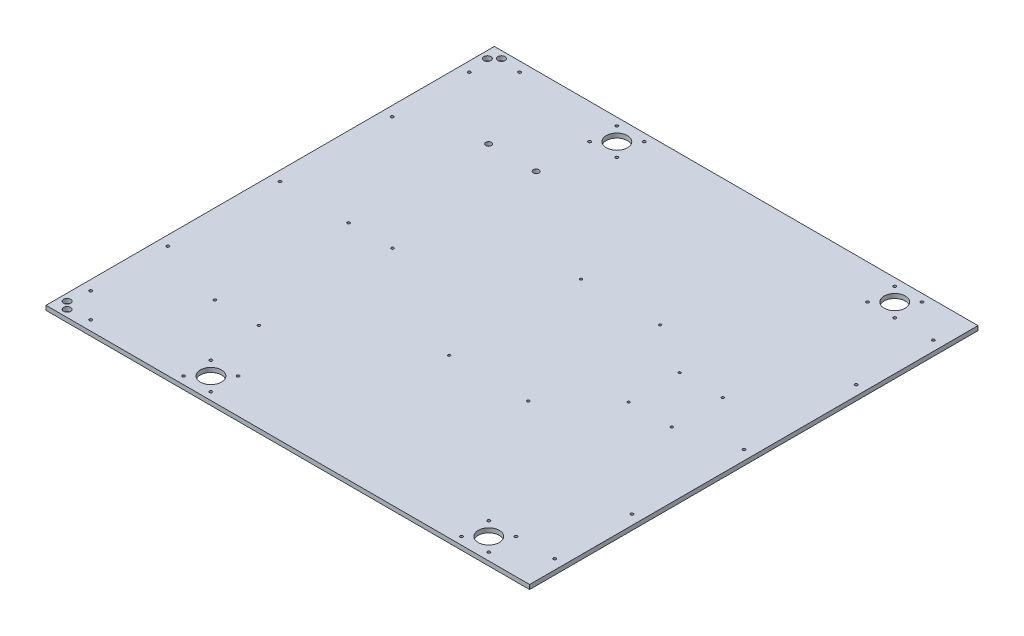
SolidWorks part; units mm, degrees
ref_plane "Front Plane" through (0, 0, 0) normal (0, 0, 1) x (1, 0, 0)
ref_plane "Top Plane" through (0, 0, 0) normal (0, 1, 0) x (1, 0, 0)
ref_plane "Right Plane" through (0, 0, 0) normal (1, 0, 0) x (0, 0, -1)
sketch "Sketch1" plane through (0, 0, 0) normal (1, 0, 0) x (0, 0, -1)
  line L0 (0, 0) -> (-510, 0)
  line L1 (-510, 0) -> (-510, 5)
  line L2 (-510, 5) -> (0, 5)
  line L6 (0, 5) -> (0, 0)
  dimension "D1" = 510
  dimension "D2" = 5
extrude "Boss-Extrude1" add sketch "Sketch1" along normal blind 550
sketch "BotthomHoles-Sketch2" plane through (0, 5, 0) normal (0, 1, 0) x (1, 0, 0)
  line L0 (550, -3.175) -> (0, -3.175) construction
  line L2 (550, 0) -> (550, -510) construction
  line L3 (550, 0) -> (0, 0) construction
  line L4 (550, -510) -> (0, -510) construction
  line L7 (0, 0) -> (0, -510) construction
  line L8 (550, 0) -> (550, -510) construction
  circle A0 centre (479.425, -24.175) radius 12
  circle A2 centre (463.925, -8.675) radius 1.5875
  circle A3 centre (494.925, -8.675) radius 1.5875
  circle A6 centre (463.925, -39.675) radius 1.5875
  circle A7 centre (494.925, -39.675) radius 1.5875
  circle A8 centre (39.6875, -11.1125) radius 1.5875
  circle A10 centre (178.925, -39.675) radius 1.5875
  circle A11 centre (147.925, -39.675) radius 1.5875
  circle A12 centre (178.925, -8.675) radius 1.5875
  circle A13 centre (147.925, -8.675) radius 1.5875
  circle A14 centre (163.425, -24.175) radius 12
  circle A15 centre (39.6875, -498.8875) radius 1.5875
  circle A16 centre (147.925, -501.325) radius 1.5875
  circle A17 centre (178.925, -501.325) radius 1.5875
  circle A18 centre (147.925, -470.325) radius 1.5875
  circle A19 centre (178.925, -470.325) radius 1.5875
  circle A20 centre (463.925, -470.325) radius 1.5875
  circle A21 centre (463.925, -501.325) radius 1.5875
  circle A22 centre (494.925, -470.325) radius 1.5875
  circle A23 centre (494.925, -501.325) radius 1.5875
  circle A25 centre (163.425, -485.825) radius 12
  circle A26 centre (479.425, -485.825) radius 12
  circle A27 centre (11.1125, -39.6875) radius 1.5875
  circle A28 centre (11.1125, -127.5) radius 1.5875
  circle A29 centre (11.1125, -255) radius 1.5875
  circle A30 centre (11.1125, -382.5) radius 1.5875
  circle A31 centre (11.1125, -470.3125) radius 1.5875
  circle A32 centre (538.8875, -470.3125) radius 1.5875
  circle A33 centre (538.8875, -382.5) radius 1.5875
  circle A34 centre (538.8875, -255) radius 1.5875
  circle A35 centre (538.8875, -127.5) radius 1.5875
  circle A36 centre (538.8875, -39.6875) radius 1.5875
  dimension "D9" = 3.175
  dimension "D10" = 24
  dimension "D13" = 3.175
  dimension "D29" = 3.175
  dimension "D2" = 8.675
  dimension "D5" = 15.5
  dimension "D6" = 31
  dimension "D7" = 15.5
  dimension "D8" = 31
  dimension "D11" = 21
  dimension "D12" = 39.6875
  dimension "D15" = 31
  dimension "D16" = 15.5
  dimension "D17" = 316
  dimension "D3" = 70.575
  dimension "D4" = 11.1125
  dimension "D18" = 8.675
  dimension "D19" = 15.5
  dimension "D20" = 31
  dimension "D21" = 11.1125
  dimension "D22" = 39.6875
  dimension "D23" = 39.6875
  dimension "D24" = 127.5
  dimension "D25" = 127.5
  dimension "D26" = 127.5
  dimension "D27" = 11.1125
  dimension "D28" = 11.1125
  dimension "D14" = 163.425
extrude "BottomHoles-Cut-Extrude1" cut sketch "BotthomHoles-Sketch2" against normal through all
sketch "BottomPSUHolesSketch2" plane through (0, 5, 0) normal (0, 1, 0) x (1, 0, 0)
  line L0 (0, 0) -> (0, -510) construction
  line L3 (550, 0) -> (0, 0) construction
  line L4 (550, -510) -> (0, -510) construction
  circle A0 centre (90.8, -256.7) radius 1.5
  circle A1 centre (140.8, -256.7) radius 1.5
  circle A2 centre (90.8, -408.7) radius 1.5
  circle A3 centre (140.8, -408.7) radius 1.5
  circle A6 centre (92.8, -99.3) radius 3.25
  circle A7 centre (146.8, -99.3) radius 3.25
  dimension "D6" = 3
  dimension "D4" = 6.5
  dimension "D1" = 152
  dimension "D2" = 50
  dimension "D3" = 90.8
  dimension "D7" = 54
  dimension "D8" = 2
  dimension "D9" = 99.3
  dimension "D5" = 101.3
extrude "BottomPSUHolesCut-Extrude1" cut sketch "BottomPSUHolesSketch2" against normal through all
sketch "BottomMainboardHolesSketch2" plane through (0, 5, 0) normal (0, 1, 0) x (1, 0, 0)
  line L0 (550, 0) -> (0, 0) construction
  line L1 (0, 0) -> (0, -510) construction
  line L2 (550, 0) -> (550, -510) construction
  line L3 (550, -510) -> (0, -510) construction
  circle A0 centre (278.5, -180) radius 1.35
  circle A1 centre (368.5, -180) radius 1.35
  circle A2 centre (278.5, -330) radius 1.35
  circle A3 centre (368.5, -330) radius 1.35
  circle A4 centre (426.7, -216) radius 1.35
  circle A5 centre (475.7, -216) radius 1.35
  circle A6 centre (426.7, -274) radius 1.35
  circle A7 centre (475.7, -274) radius 1.35
  dimension "D6" = 2.7
  dimension "D7" = 2.7
  dimension "D1" = 90
  dimension "D2" = 150
  dimension "D3" = 180
  dimension "D4" = 58
  dimension "D5" = 49
  dimension "D8" = 216
  dimension "D9" = 278.5
  dimension "D10" = 74.3
  dimension "D11" = 236
extrude "BottomMainboardHolesCut-Extrude1" cut sketch "BottomMainboardHolesSketch2" against normal through all
sketch "CableHolesSketch2" plane through (0, 5, 0) normal (0, 1, 0) x (1, 0, 0)
  line L0 (550, 0) -> (0, 0) construction
  line L1 (550, -510) -> (0, -510) construction
  line L2 (0, 0) -> (0, -510) construction
  circle A0 centre (8, -494) radius 4
  circle A1 centre (16, -502) radius 4
  circle A2 centre (8, -16) radius 4
  circle A3 centre (16, -8) radius 4
  dimension "D6" = 8
  dimension "D1" = 16
  dimension "D2" = 16
  dimension "D3" = 16
  dimension "D4" = 8
  dimension "D5" = 8
  dimension "D7" = 8
extrude "CableHolesCut-Extrude1" cut sketch "CableHolesSketch2" against normal through all
equation "\"LowerRailWidth\"= 2.00in"
equation "\"RailThickness\"= .125in'Spec"
equation "\"StepperHoleDiameter\"= 24mm"
equation "\"StepperMountingHoleDiameter\"= 3.175mm"
equation "\"SideRailLength\"= 550mm"
equation "\"StepperMountingHoleDistance\"= 31mm'Spec"
equation "\"StepperMountingHoleOffsetFromLeftOrRightSide\"= \"StepperMountingHoleOffsetFromItsSide\" + \"RailThickness\""
equation "\"HoleOffsetFromEdge\"= \"RailThickness\" * 2.5"
equation "\"HoleOffsetFromSide\"= \"RailThickness\" * 3.5"
equation "\"StepperMountingHoleOffsetFromItsSide\"= 5.5mm'Spec"
equation "\"FasteningHoleDiameter\"= .125in"
equation "\"D2@BotthomHoles-Sketch2\" = \"StepperMountingHoleOffsetFromLeftOrRightSide\""
equation "\"D5@BotthomHoles-Sketch2\" = \"StepperMountingHoleDistance\" / 2"
equation "\"D6@BotthomHoles-Sketch2\" = \"StepperMountingHoleDistance\""
equation "\"D7@BotthomHoles-Sketch2\" = \"StepperMountingHoleDistance\" / 2"
equation "\"D8@BotthomHoles-Sketch2\" = \"StepperMountingHoleDistance\""
equation "\"D9@BotthomHoles-Sketch2\" = \"StepperMountingHoleDiameter\""
equation "\"D10@BotthomHoles-Sketch2\" = \"StepperHoleDiameter\""
equation "\"D1@Boss-Extrude1\"=\"SideRailLength\""
equation "\"BedThirdSize\"= 70mm"
equation "\"BedInnerSquareWidth\"= \"BedThirdSize\" * 3'Equals 210"
equation "\"BedInnerSquareLength\"= \"BedInnerSquareWidth\""
equation "\"BedLWidth\"= \"BedThirdSize\"'Equals 70"
equation "\"BedLength\"= \"BedInnerSquareLength\" + \"BedLWidth\" * 2 + \"BedIncreasedByLength\"'Equals 350"
equation "\"DistanceBetweenFrontToBackStepperHoles\"= \"BedLength\" - \"DistanceFromBedFrontToFirstLeftStepperHole\"'Equals 316"
equation "\"DistanceFromBedFrontToFirstLeftStepperHole\"= \"LeadScrewNutPadSize\" + 10mm'Equals 34"
equation "\"DistanceFromFrontSideToBedFront\"= \"RailThickness\" + \"BeltTensionerDepth\" + 10mm'Equals 36.575"
equation "\"20TGT2PulleyDiameter\"= 17.9mm'Spec"
equation "\"BeltTensionerBackWallThickness\"= 4mm"
equation "\"BeltTensionerSpaceBetweenPulleyAndWall\"= 1.5mm"
equation "\"BeltTensionerInnerDepth\"= \"20TGT2PulleyDiameter\" + \"BeltTensionerSpaceBetweenPulleyAndWall\""
equation "\"BeltTensionerDepth\"= \"BeltTensionerBackWallThickness\" + \"BeltTensionerInnerDepth\"'Equals 23.4"
equation "\"BedIncreasedByLength\"= 0mm"
equation "\"LowerCornerBlockWidth\"= \"LowerRailWidth\" - \"RailThickness\" * 2'Room for left front stepper"
equation "\"D12@BotthomHoles-Sketch2\"=\"CornerEnclosureOffset\""
equation "\"D13@BotthomHoles-Sketch2\"=\"FasteningHoleDiameter\""
equation "\"CornerEnclosureOffset\"= \"LowerCornerBlockWidth\" - \"HoleOffsetFromEdge\" + \"RailThickness\""
equation "\"LowerCornerBlockY1FromSide\"= \"HoleOffsetFromSide\""
equation "\"D15@BotthomHoles-Sketch2\"=\"StepperMountingHoleDistance\""
equation "\"D16@BotthomHoles-Sketch2\"=\"StepperMountingHoleDistance\"/2"
equation "\"D17@BotthomHoles-Sketch2\"=\"DistanceBetweenFrontToBackStepperHoles\""
equation "\"DistanceFromFrontSideToFirstLeftStepperHole\"= \"DistanceFromFrontSideToBedFront\" + \"DistanceFromBedFrontToFirstLeftStepperHole\"'Equals 70.575"
equation "\"LeadScrewNutMountingHoleFlangeDiameter\"= 22mm'Spec"
equation "\"LeadScrewNutPadSize\"= \"LeadScrewNutMountingHoleFlangeDiameter\" + 2mm'Equals 24"
equation "\"D3@BotthomHoles-Sketch2\"=\"DistanceFromFrontSideToFirstLeftStepperHole\""
equation "\"LowerEnclosureThickness\"= 5mm"
equation "\"FrontBackRailLength\"= 510mm"
equation "\"D4@BotthomHoles-Sketch2\"=\"LowerCornerBlockY1FromSide\""
equation "\"D1@Sketch1\"=\"FrontBackRailLength\""
equation "\"D18@BotthomHoles-Sketch2\"=\"StepperMountingHoleOffsetFromLeftOrRightSide\""
equation "\"D19@BotthomHoles-Sketch2\"=\"StepperMountingHoleDistance\"/2"
equation "\"D20@BotthomHoles-Sketch2\"=\"StepperMountingHoleDistance\""
equation "\"D21@BotthomHoles-Sketch2\"=\"LowerCornerBlockY1FromSide\""
equation "\"D22@BotthomHoles-Sketch2\"=\"CornerEnclosureOffset\""
equation "\"D23@BotthomHoles-Sketch2\"=\"CornerEnclosureOffset\""
equation "\"FrontOrBackEnclosureOffsets\"= \"FrontBackRailLength\" / 4"
equation "\"D24@BotthomHoles-Sketch2\"=\"FrontOrBackEnclosureOffsets\""
equation "\"D25@BotthomHoles-Sketch2\"=\"FrontOrBackEnclosureOffsets\""
equation "\"D26@BotthomHoles-Sketch2\"=\"FrontOrBackEnclosureOffsets\""
equation "\"D27@BotthomHoles-Sketch2\"=\"LowerCornerBlockY1FromSide\""
equation "\"D28@BotthomHoles-Sketch2\"=\"LowerCornerBlockY1FromSide\""
equation "\"D29@BotthomHoles-Sketch2\"=\"FasteningHoleDiameter\""
equation "\"D2@Sketch1\"=\"LowerEnclosureThickness\""
equation "\"24VPSUMountingHolesShortDistanceBetween\"= 50mm'Yours may differ"
equation "\"24VPSUMountingHolesLongDistanceBetween\"= 152mm'Yours may differ"
equation "\"24VPSUMountingHoleOffsetFromEitherSide\"= 30mm'Yours may differ"
equation "\"24VPSUMountingHoleOffsetFromEdge\"= \"24VPSUMountingHoleOffsetFromEitherSide\" + \"LowerRailWidth\" + 10mm'Yours may differ"
equation "\"24VPSUMountingHoleDiameter\"= 3mm'Yours may differ"
equation "\"D2@BottomPSUHolesSketch2\" = \"24VPSUMountingHolesShortDistanceBetween\""
equation "\"D1@BottomPSUHolesSketch2\" = \"24VPSUMountingHolesLongDistanceBetween\""
equation "\"D3@BottomPSUHolesSketch2\" = \"24VPSUMountingHoleOffsetFromEdge\""
equation "\"D6@BottomPSUHolesSketch2\" = \"24VPSUMountingHoleDiameter\""
equation "\"RPi4BoardLength\"= 85mm'Spec"
equation "\"RPi4BoardWidth\"= 56mm'Spec"
equation "\"RPi4BoardMountingHoleOffsetFromEdge\"= 3.5mm'Spec"
equation "\"RPi4BoardMountingHoleDiameter\"= 2.7mm'Spec"
equation "\"OctopusV1.1BoardMountingHoleOffsetFromAllEdges\"= 3.5mm'Spec"
equation "\"OctopusV1.1BoardMountingHoleLengthDistanceBetween\"= 150mm'Spec"
equation "\"OctopusV1.1BoardMountingHoleWidthDistanceBetween\"= 90mm'Spec"
equation "\"D2@BottomMainboardHolesSketch2\" = \"OctopusV1.1BoardMountingHoleLengthDistanceBetween\""
equation "\"D3@BottomMainboardHolesSketch2\" =  ( \"FrontBackRailLength\" - \"OctopusV1.1BoardMountingHoleLengthDistanceBetween\" )  / 2"
equation "\"D4@BottomMainboardHolesSketch2\" = \"RPi4BoardMountingHoleLengthDistanceBetween\""
equation "\"D5@BottomMainboardHolesSketch2\"=\"RPi4BoardWidth\"- \"RPi4BoardMountingHoleOffsetFromEdge\" * 2"
equation "\"D6@BottomMainboardHolesSketch2\" = \"OctopusV1.1BoardMountingHoleDiameter\""
equation "\"D7@BottomMainboardHolesSketch2\" = \"RPi4BoardMountingHoleDiameter\""
equation "\"RPi4BoardMountingHoleLengthDistanceBetween\"= 58mm'Spec"
equation "\"OctopusV1.1BoardMountingHoleDiameter\"= 2.7mm'Spec"
equation "\"D1@BottomMainboardHolesSketch2\" = \"OctopusV1.1BoardMountingHoleWidthDistanceBetween\""
equation "\"D8@BottomMainboardHolesSketch2\" =  ( \"FrontBackRailLength\" - \"RPi4BoardLength\" )  / 2 + \"RPi4BoardMountingHoleOffsetFromEdge\""
equation "\"D9@BottomMainboardHolesSketch2\" = \"SideRailLength\" / 2 + \"OctopusV1.1BoardMountingHoleOffsetFromAllEdges\""
equation "\"D10@BottomMainboardHolesSketch2\"= \"LowerRailWidth\" + \"RPi4BoardMountingHoleOffsetFromEdge\" + \"EnclosurePartsOffsetFromFrameInnerEdge\""
equation "\"RCNUN5VMountingHoleDiameter\"= 6.5mm'Spec"
equation "\"RCNUN5VHeight\"= 57mm'Spec"
equation "\"RCNUN5VMountingHoleWidthDistance\"= 54mm'Spec. STL Is incorrect?"
equation "\"D4@BottomPSUHolesSketch2\"=\"RCNUN5VMountingHoleDiameter\""
equation "\"D7@BottomPSUHolesSketch2\"=\"RCNUN5VMountingHoleWidthDistance\""
equation "\"D8@BottomPSUHolesSketch2\"=(\"RCNUN5VMountingHoleWidthDistance\" - \"24VPSUMountingHolesShortDistanceBetween\")/2"
equation "\"D9@BottomPSUHolesSketch2\"=\"LowerRailWidth\" + \"RCNUN5VHeight\"/2 + \"EnclosurePartsOffsetFromFrameInnerEdge\""
equation "\"EnclosurePartsOffsetFromFrameInnerEdge\"= 20mm"
equation "\"D5@BottomPSUHolesSketch2\"= \"LowerRailWidth\" + \"EnclosurePartsOffsetFromFrameInnerEdge\" + ( \"24VPSULength\" - \"24VPSUMountingHolesLongDistanceBetween\" ) / 2"
equation "\"24VPSULength\"= 213mm'Spec"
equation "\"LowerRailCableHoleDiameter\"= 8mm"
equation "\"LowerRailCableHoleOffsetFromSide\"= 8mm"
equation "\"LowerRailCableHoleOffsetFromEdge\"= 16mm"
equation "\"D1@CableHolesSketch2\"=\"LowerRailCableHoleOffsetFromEdge\""
equation "\"D2@CableHolesSketch2\"=\"LowerRailCableHoleOffsetFromEdge\""
equation "\"D3@CableHolesSketch2\"=\"LowerRailCableHoleOffsetFromEdge\""
equation "\"D4@CableHolesSketch2\"=\"LowerRailCableHoleOffsetFromSide\""
equation "\"D5@CableHolesSketch2\"=\"LowerRailCableHoleOffsetFromSide\""
equation "\"D6@CableHolesSketch2\"=\"LowerRailCableHoleDiameter\""
equation "\"D7@CableHolesSketch2\"=\"LowerRailCableHoleOffsetFromSide\""
